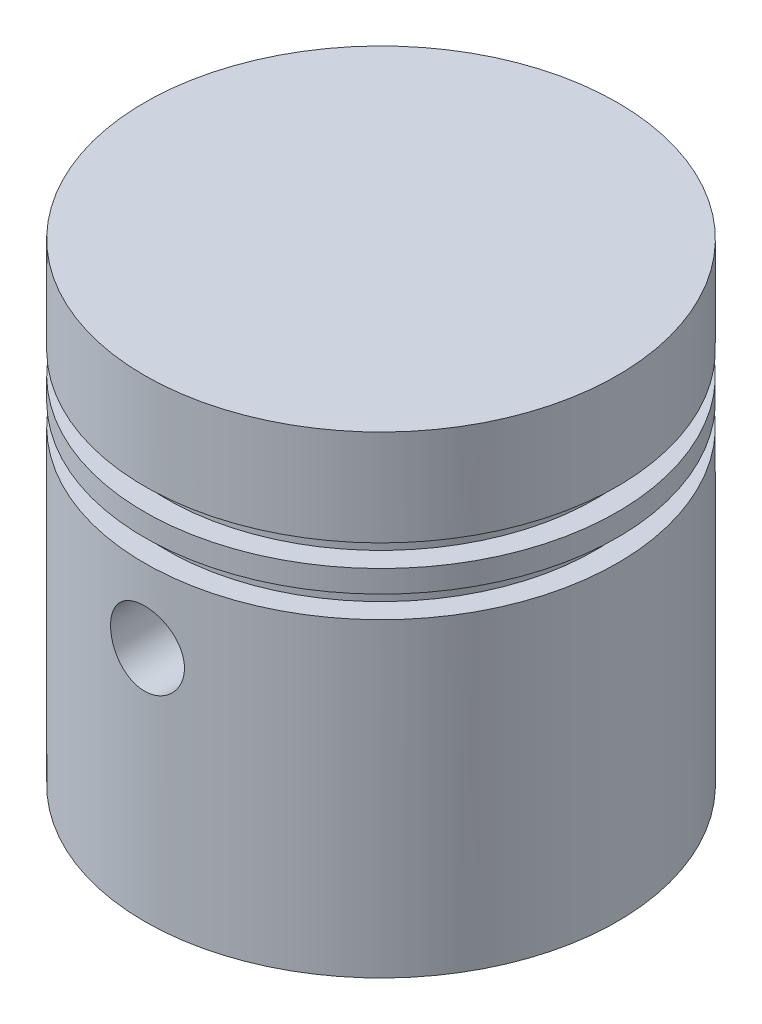
SolidWorks part; units mm, degrees
material "6061 Alloy"
ref_plane "Front Plane" through (0, 0, 0) normal (0, 0, 1) x (1, 0, 0)
ref_plane "Top Plane" through (0, 0, 0) normal (0, 1, 0) x (1, 0, 0)
ref_plane "Right Plane" through (0, 0, 0) normal (1, 0, 0) x (0, 0, -1)
sketch "Sketch1" plane through (0, 0, 0) normal (0, 1, 0) x (1, 0, 0)
  circle A0 centre (0, 0) radius 8
  dimension "D1" = 16
extrude "Boss-Extrude1" add sketch "Sketch1" along normal blind 16
sketch "Sketch2" plane through (0, 0, 0) normal (0, -1, 0) x (1, 0, 0)
  circle A0 centre (0, 0) radius 6.5
  dimension "D1" = 13
extrude "Cut-Extrude1" cut sketch "Sketch2" against normal blind 5
sketch "Sketch3" plane through (0, 0, 0) normal (0, -1, 0) x (1, 0, 0)
  circle A0 centre (0, 0) radius 5
  dimension "D1" = 10
extrude "Cut-Extrude2" cut sketch "Sketch3" against normal blind 12
sketch "Sketch4" plane through (0, 0, 0) normal (0, 0, 1) x (1, 0, 0)
  line L0 (8, 16) -> (-8, 16) construction
  circle A0 centre (0, 8) radius 1.25
  dimension "D1" = 2.5
  dimension "D2" = 8
  dimension "D3" = 8
extrude "Cut-Extrude3" cut sketch "Sketch4" against normal through all both and the other way through all
sketch "Sketch5" plane through (0, 0, 0) normal (0, -1, 0) x (1, 0, 0)
  circle A0 centre (0, 0) radius 8
  circle A1 centre (0, 0) radius 7.25
  dimension "D1" = 16
  dimension "D2" = 14.5
extrude "Cut-Extrude5" cut sketch "Sketch5" against normal blind 0.75 from offset 10.5 offset against normal yes
extrude "Cut-Extrude6" cut sketch "Sketch5<3>" against normal blind 0.75 from offset 12
sketch "Sketch5<3>" plane through (0, 0, 0) normal (0, -1, 0) x (1, 0, 0) same geometry as "Sketch5"
